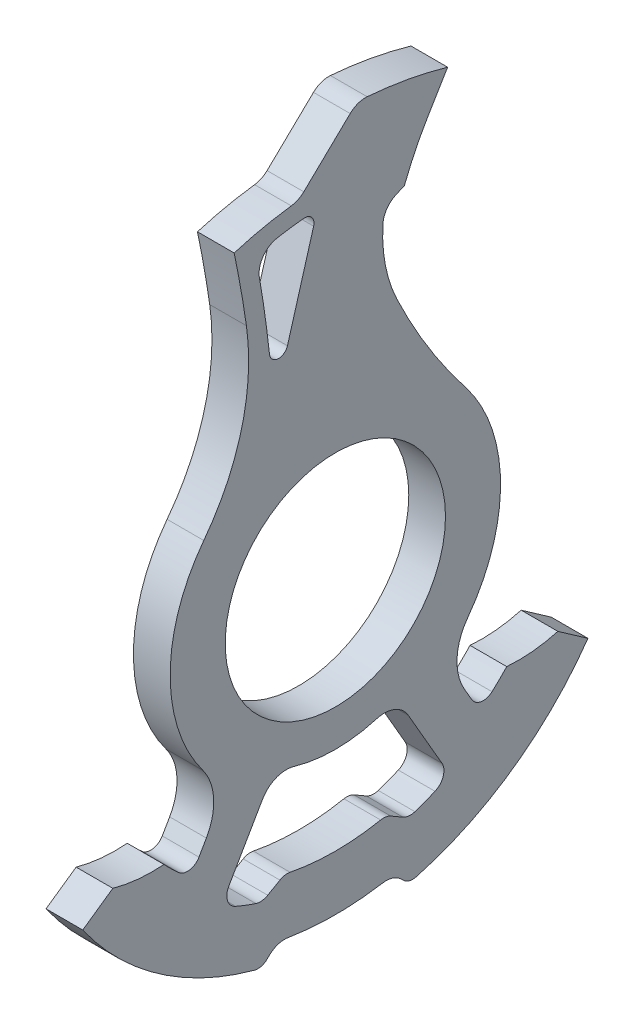
SolidWorks part; units mm, degrees
material "AR500"
ref_plane "Front Plane" through (0, 0, 0) normal (0, 0, 1) x (1, 0, 0)
ref_plane "Top Plane" through (0, 0, 0) normal (0, 1, 0) x (1, 0, 0)
ref_plane "Right Plane" through (0, 0, 0) normal (1, 0, 0) x (0, 0, -1)
other "Center of Mass"
sketch "Sketch1" plane through (0, 0, 0) normal (1, 0, 0) x (0, 0, -1)
  circle A0 centre (0, 0) radius 139.7 construction
  circle A1 centre (0, 0) radius 106.68 construction
  circle A2 centre (0, 0) radius 38.1 construction
  dimension "D1" = 279.4
  dimension "D2" = 33.02
  dimension "D3" = 76.2
sketch "Sketch2" plane through (0, 0, 0) normal (1, 0, 0) x (0, 0, -1)
  line L0 (0, 0) -> (38.858, 134.187) construction
  line L1 (38.858, 134.187) -> (32.2885, 123.3181)
  line L2 (0, 0) -> (0, 61.679) construction
  line L3 (7.5549, 139.4956) -> (-12.768, 119.9725)
  line L4 (-35.0051, 115.4602) -> (-40.3483, 140.8902) construction
  line L5 (23.88, 106.192) -> (20.1469, 96.5425) construction
  line L6 (23.88, 106.192) -> (16.9106, 103.1109)
  line L7 (16.9106, 103.1109) -> (16.6566, 100.7528)
  line L8 (-35.0051, 115.4602) -> (-4.6687, 124.6576) construction
  line L10 (0, -100.33) -> (0, 0) construction
  line L11 (-20.0866, -98.2987) -> (-25.4, -103.6121)
  line L16 (-49.9001, -64.1593) -> (-37.6706, -42.9773)
  line L17 (87.3871, -61.1891) -> (76.9839, -53.9047)
  line L18 (-87.3871, -61.1891) -> (-76.9839, -53.9047)
  line L19 (49.9001, -64.1593) -> (37.6706, -42.9773)
  line L24 (53.8815, -53.8815) -> (0, 0) construction
  line L25 (20.0866, -98.2987) -> (25.4, -103.6121)
  circle A0 centre (0, 0) radius 139.7 construction
  arc A1 (38.858, 134.187) -> (7.5549, 139.4956) centre (0, 0) ccw
  arc A2 (-12.768, 119.9725) -> (-35.0051, 115.4602) centre (0, 0) ccw
  arc A3 (32.2885, 123.3181) -> (23.88, 106.192) centre (125.9607, 66.6999) ccw
  arc A4 (44.9569, 35.2845) -> (37.6706, -42.9773) centre (0, 0) cw
  circle A5 centre (0, 0) radius 38.1 construction
  arc A6 (21.2843, 73.5004) -> (16.6566, 100.7528) centre (67.1642, 95.3105) cw
  arc A7 (-35.0051, 115.4602) -> (-30.7712, 91.5455) centre (-407.8633, 37.1165) cw
  arc A8 (-30.7712, 91.5455) -> (-45.5098, 34.5685) centre (-106.1896, 80.6597) cw
  arc A9 (-45.5098, 34.5685) -> (-37.6706, -42.9773) centre (0, 0) ccw
  arc A10 (-87.3871, -61.1891) -> (-25.4, -103.6121) centre (0, 0) ccw
  circle A11 centre (0, 0) radius 106.68 construction
  arc A18 (-76.9839, -53.9047) -> (-59.2852, -55.6031) centre (-63.357, -4.9665) ccw
  arc A19 (-59.2852, -55.6031) -> (-49.9001, -64.1593) centre (0, 0) ccw
  arc A20 (-20.0866, -98.2987) -> (20.0866, -98.2987) centre (0, 0) ccw
  arc A21 (59.2852, -55.6031) -> (49.9001, -64.1593) centre (0, 0) cw
  arc A22 (76.9839, -53.9047) -> (59.2852, -55.6031) centre (63.357, -4.9665) cw
  arc A23 (87.3871, -61.1891) -> (25.4, -103.6121) centre (0, 0) cw
  circle A24 centre (0, 0) radius 38.1
  arc A25 (21.2843, 73.5004) -> (44.9569, 35.2845) centre (204.8038, 160.7405) ccw
  dimension "D4" = 19.05
  dimension "D11" = 57.15
  dimension "D13" = 50.8
  dimension "D14" = 381
  dimension "D16" = 76.2
  dimension "D19" = 6.35
  dimension "D21" = 55
  dimension "D26" = 17.78
  dimension "D22" = 25.4
  dimension "D23" = 50.8
  dimension "D27" = 12.7
  dimension "D29" = 203.2
  dimension "D1" = 15
  dimension "D2" = 16.15
  dimension "D3" = 15
  dimension "D5" = 31.75
  dimension "D6" = 12.7
  dimension "D7" = 31.75
  dimension "D8" = 5
  dimension "D9" = 45
  dimension "D10" = 10
  dimension "D12" = 7.62
  dimension "D15" = 85
  dimension "D17" = 76.2
  dimension "D18" = 25.4
  dimension "D20" = 45
  dimension "D24" = 12.7
  dimension "D25" = 45
  dimension "D28" = 30
extrude "Boss-Extrude1" add sketch "Sketch2" along normal mid plane 12.7
sketch "Sketch3" plane through (6.35, 0, 0) normal (1, 0, 0) x (0, 0, -1)
  line L1 (-7.513, 109.7387) -> (-16.5762, 78.441)
  line L2 (16.6566, 100.7528) -> (16.9106, 103.1109) construction
  line L3 (-3.2803, 66.3447) -> (4.4504, 105.5668) construction
  line L4 (16.9106, 103.1109) -> (-8.0099, 108.0227) construction
  arc A0 (-12.768, 119.9725) -> (-35.0051, 115.4602) centre (0, 0) ccw construction
  arc A1 (-30.7712, 91.5455) -> (-35.0051, 115.4602) centre (-407.8633, 37.1165) ccw construction
  arc A2 (-7.513, 109.7387) -> (-10.8645, 113.7825) centre (-10.5627, 110.6219) ccw
  arc A3 (-12.768, 119.9725) -> (-35.0051, 115.4602) centre (0, 0) ccw construction
  arc A4 (-30.7712, 91.5455) -> (-35.0051, 115.4602) centre (-407.8633, 37.1165) ccw construction
  arc A5 (-10.8645, 113.7825) -> (-27.6085, 110.9156) centre (0, 0) ccw
  arc A6 (-22.7823, 78.981) -> (-27.6085, 110.9156) centre (-407.8633, 37.1165) ccw
  arc A7 (-24.4863, 92.4527) -> (-27.6085, 110.9156) centre (-407.8633, 37.1165) ccw construction
  arc A8 (-12.096, 113.6582) -> (-27.6085, 110.9156) centre (0, 0) ccw construction
  arc A14 (-22.7823, 78.981) -> (-16.5762, 78.441) centre (-19.6259, 79.3242) ccw
  point P18 (16.9106, 103.1109)
  dimension "D5" = 3.175
  dimension "D7" = 3.175
  dimension "D3" = 10
  dimension "D4" = 25.4
  dimension "D1" = 6.35
extrude "Cut-Extrude1" cut sketch "Sketch3" against normal through all
fillet "Fillet1" radius 7.62 6 edges at (0, 103.1109, -16.9106) (0, 110.9156, 27.6085) (0, 139.4956, -7.5549) (0, 119.9725, 12.768) (0, -98.2987, -20.0866) (0, -98.2987, 20.0866)
fillet "Fillet4" radius 19.05 2 edges at (0, -42.9773, -37.6706) (0, -42.9773, 37.6706)
fillet "Fillet2" radius 4.572 4 edges at (0, -103.6121, 25.4) (0, -103.6121, -25.4) (0, -64.1593, -49.9001) (0, -64.1593, 49.9001)
sketch "Sketch4" plane through (6.35, 0, 0) normal (1, 0, 0) x (0, 0, -1)
  line L0 (-21.1843, -46.1721) -> (-39.646, -78.1487)
  line L1 (-44.6265, -55.0252) -> (-47.1846, -59.4559) construction
  line L2 (0, -81.28) -> (0, -50.8)
  line L3 (-25.3274, -83.8901) -> (-17.5035, -79.373)
  line L4 (-11.6185, -94.3061) -> (-25.8749, -102.5371) construction
  arc A0 (-39.646, -78.1487) -> (-25.3274, -83.8901) centre (0, 0) ccw
  arc A1 (0, -50.8) -> (-21.1843, -46.1721) centre (0, 0) cw
  circle A2 centre (0, 0) radius 38.1 construction
  circle A3 centre (0, 0) radius 106.68 construction
  arc A4 (-17.5035, -79.373) -> (0, -81.28) centre (0, 0) ccw
  arc A5 (-16.2916, -98.9984) -> (16.2916, -98.9984) centre (0, 0) ccw construction
  arc A6 (-87.3871, -61.1891) -> (-27.9851, -102.9439) centre (0, 0) ccw construction
  arc A7 (-16.2916, -98.9984) -> (-22.9171, -101.1292) centre (-17.5289, -106.5173) ccw construction
  dimension "D1" = 50.8
  dimension "D3" = 19.05
  dimension "D4" = 19.05
  dimension "D2" = 15.875
  dimension "D5" = 30
  dimension "D6" = 15.875
extrude "Cut-Extrude2" cut sketch "Sketch4" against normal through all
mirror "Mirror1" about plane through (-6.35, -81.28, 0) normal (0, 0, -1) of "Cut-Extrude2"
fillet "Fillet3" radius 5.08 6 edges at (0, -78.1487, -39.646) (0, -83.8901, -25.3274) (0, -79.373, -17.5035) (0, -79.373, 17.5035) (0, -83.8901, 25.3274) (0, -78.1487, 39.646)
fillet "Fillet5" radius 9.525 2 edges at (0, -46.1721, -21.1843) (0, -46.1721, 21.1843)
ref_axis "Axis1" through (6.35, 0, 0) along (-1, 0, 0)
